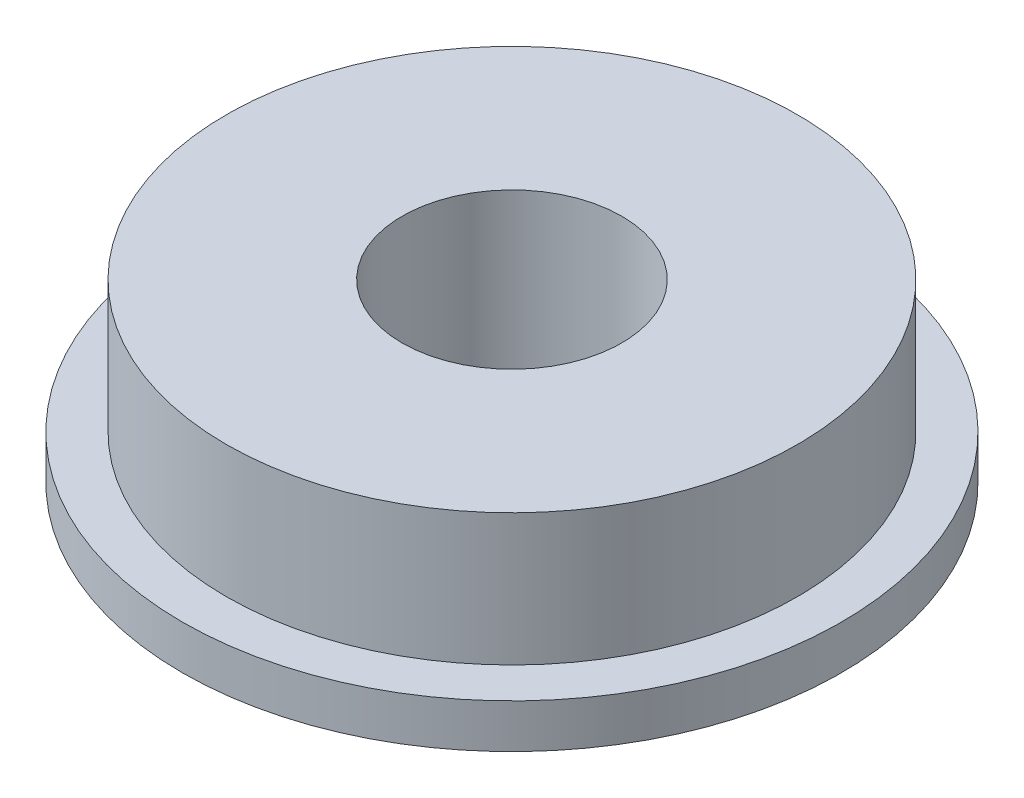
SolidWorks part; units mm, degrees
ref_plane "Front Plane" through (0, 0, 0) normal (0, 0, 1) x (1, 0, 0)
ref_plane "Top Plane" through (0, 0, 0) normal (0, 1, 0) x (1, 0, 0)
ref_plane "Right Plane" through (0, 0, 0) normal (1, 0, 0) x (0, 0, -1)
sketch "Sketch1" plane through (0, 0, 0) normal (0, 1, 0) x (1, 0, 0)
  circle A0 centre (0, 0) radius 2.5
  circle A1 centre (0, 0) radius 6.5
  circle A2 centre (0, 0) radius 7.5
  dimension "D1" = 5
  dimension "D2" = 13
  dimension "D3" = 15
extrude "Boss-Extrude1" add sketch "Sketch1" along normal blind 1 contours A1 A0 | A2 A1 region at (-6.3162, 0, 0) region at (-7.2879, 0, 0)
extrude "Boss-Extrude2" add sketch "Sketch1<3>" along normal blind 3 from surface contours A1 A0 region at (-6.3162, 0, 0) starting at face at (0, 1, 2.5)
sketch "Sketch1<3>" plane through (0, 0, 0) normal (0, 1, 0) x (1, 0, 0) same geometry as "Sketch1"
